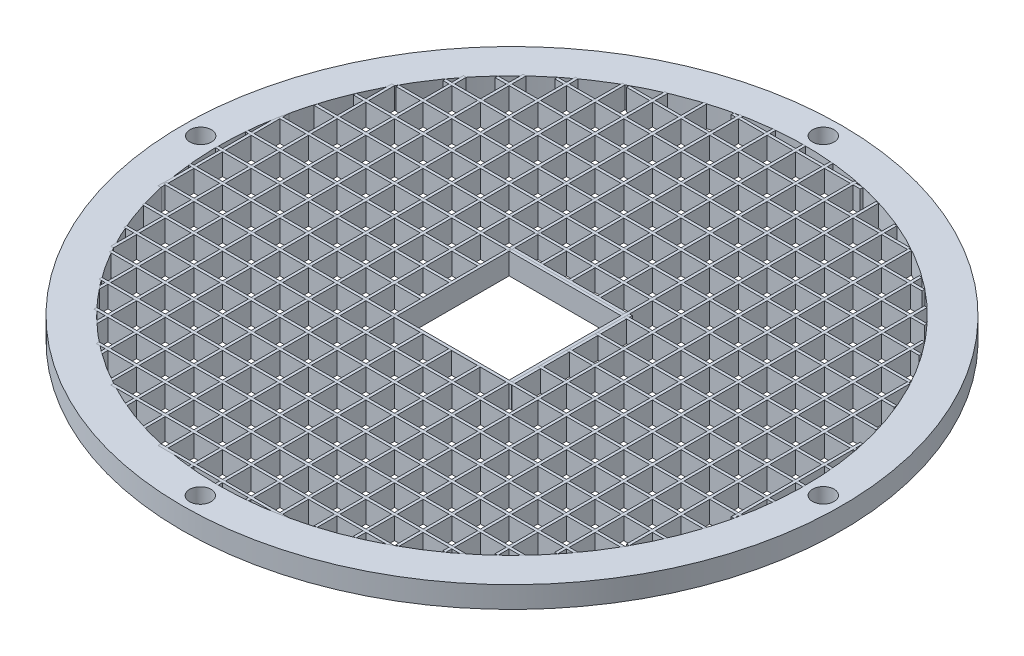
SolidWorks part; units mm, degrees
ref_plane "Front Plane" through (0, 0, 0) normal (0, 0, 1) x (1, 0, 0)
ref_plane "Top Plane" through (0, 0, 0) normal (0, 1, 0) x (1, 0, 0)
ref_plane "Right Plane" through (0, 0, 0) normal (1, 0, 0) x (0, 0, -1)
sketch "Sketch2" plane through (0, 0, 0) normal (0, 1, 0) x (1, 0, 0)
  circle A1 centre (0, 0) radius 41
  circle A2 centre (0, 0) radius 46
  point P208 (0, 0)
extrude "Boss-Extrude2" add sketch "Sketch2" along normal blind 3
sketch "Sketch4" plane through (0, 3, 0) normal (0, 1, 0) x (1, 0, 0)
  line L0 (0, 41) -> (0, 7.9933)
  line L1 (4, 40.8044) -> (4, 7.9933)
  line L2 (8, 40.2119) -> (8, -40.2119)
  line L3 (12, 39.2046) -> (12, -39.2046)
  line L4 (16, 37.7492) -> (16, -37.7492)
  line L5 (20, 35.7911) -> (20, -35.7911)
  line L6 (24, 33.2415) -> (24, -33.2415)
  line L7 (28, 29.95) -> (28, -29.95)
  line L8 (32, 25.632) -> (32, -25.632)
  line L9 (36, 19.6214) -> (36, -19.6214)
  line L10 (40, 9) -> (40, -9)
  line L11 (-41, 0) -> (-8, 0)
  line L12 (-4, 40.8044) -> (-4, 7.9933)
  line L13 (-8, 40.2119) -> (-8, -40.2119)
  line L14 (-12, 39.2046) -> (-12, -39.2046)
  line L15 (-16, 37.7492) -> (-16, -37.7492)
  line L16 (-20, 35.7911) -> (-20, -35.7911)
  line L17 (-24, 33.2415) -> (-24, -33.2415)
  line L18 (-28, 29.95) -> (-28, -29.95)
  line L19 (-32, 25.632) -> (-32, -25.632)
  line L20 (-36, 19.6214) -> (-36, -19.6214)
  line L21 (-40, 9) -> (-40, -9)
  line L22 (-40.8042, -4) -> (-8, -4)
  line L23 (-44, 41) -> (-44, -41) [skipped]
  line L24 (44, 41) -> (44, -41) [skipped]
  line L25 (-40.2119, -8) -> (40.2119, -8)
  line L26 (-39.2046, -12) -> (39.2046, -12)
  line L27 (-37.7492, -16) -> (37.7492, -16)
  line L28 (-35.7911, -20) -> (35.7911, -20)
  line L29 (-33.2415, -24) -> (33.2415, -24)
  line L30 (-29.95, -28) -> (29.95, -28)
  line L31 (-25.632, -32) -> (25.632, -32)
  line L32 (-19.6214, -36) -> (19.6214, -36)
  line L33 (-9, -40) -> (9, -40)
  line L34 (-9, 40) -> (9, 40)
  line L35 (-19.6214, 36) -> (19.6214, 36)
  line L36 (-25.632, 32) -> (25.632, 32)
  line L37 (-29.95, 28) -> (29.95, 28)
  line L38 (-33.2415, 24) -> (33.2415, 24)
  line L39 (-35.7911, 20) -> (35.7911, 20)
  line L40 (-37.7492, 16) -> (37.7492, 16)
  line L41 (-39.2046, 12) -> (39.2046, 12)
  line L42 (-40.2119, 8) -> (40.2119, 8)
  line L43 (-40.8042, 4) -> (-8, 4)
  line L44 (8, -8.0372) -> (-8, -8.0372)
  line L45 (8, -8.0372) -> (8, 7.9933)
  line L46 (8, 7.9933) -> (-8, 7.9933)
  line L47 (-8, -8.0372) -> (-8, 7.9933)
  line L48 (-4, -8.0372) -> (-4, -40.8044)
  line L49 (8, 4) -> (40.8042, 4)
  line L50 (0, -8.0372) -> (0, -41)
  line L51 (4, -8.0372) -> (4, -40.8044)
  line L52 (8, 0) -> (41, 0)
  line L53 (8, -4) -> (40.8042, -4)
  circle A0 centre (0, 0) radius 41 construction
  point P96 (-7.2006, -7.0422)
  point P108 (8, 7.9933)
  point P109 (-8, -8.0372)
  dimension "D1" = 12
  dimension "D2" = 12
extrude "Extrude-Thin5" add sketch "Sketch4" against normal blind 3 separate body thin thin type one direction wall 0.4
sketch "Sketch5" plane through (0, 0, 0) normal (0, -1, 0) x (1, 0, 0)
  circle A0 centre (0, -43.4524) radius 1.5
  circle A1 centre (-43.4524, 0) radius 1.5
  circle A3 centre (43.4524, 0) radius 1.5
  circle A4 centre (0, 43.4524) radius 1.5 [skipped]
  point P11 (0, 0)
  dimension "D1" = 4
extrude "Cut-Extrude1" cut sketch "Sketch5" against normal blind 3
sketch "Sketch6" plane through (0, 3, 0) normal (0, 1, 0) x (1, 0, 0)
  point P0 (0, -43.5259)
  point P36 (0, 3)
sketch "Sketch7" plane through (0, 3, 0) normal (0, 1, 0) x (1, 0, 0)
  circle A0 centre (0, -43.5) radius 1.5
  circle A1 centre (0, 0) radius 41 construction
  point P4 (0, -43.5)
  dimension "D1" = 43.5
extrude "Cut-Extrude3" cut sketch "Sketch7" against normal through all
